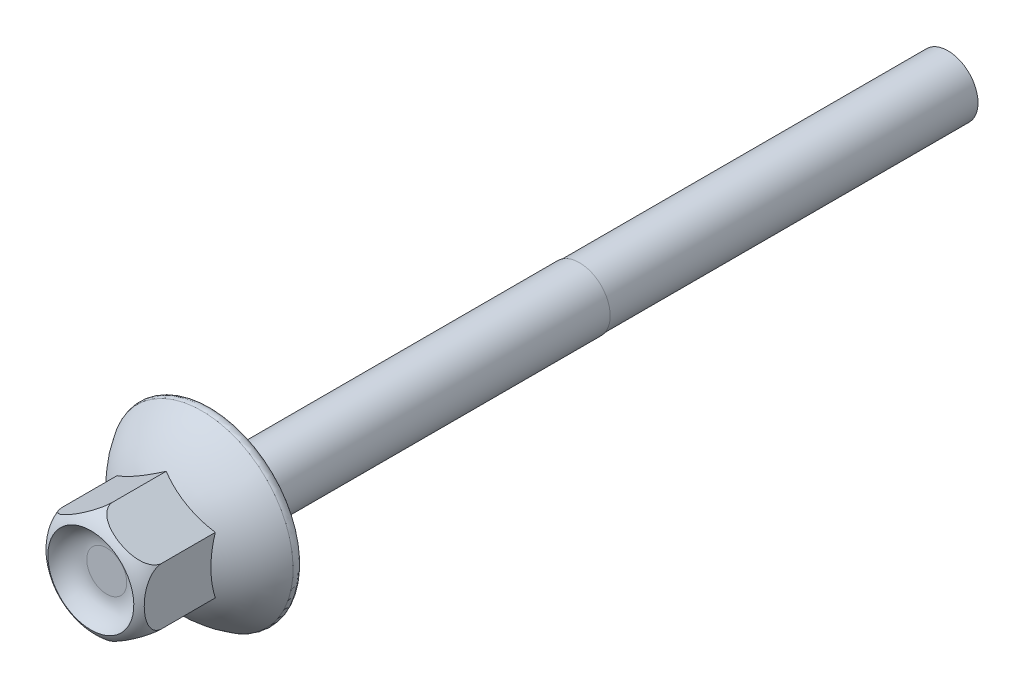
SolidWorks part; units mm, degrees
note: '?' marks a value the reader was unsure of.
ref_plane "Plane1" through (0, 0, 0) normal (0, 0, 1) x (1, 0, 0)
ref_plane "Plane2" through (0, 0, 0) normal (0, 1, 0) x (-1, 0, 0)
ref_plane "Plane3" through (0, 0, 0) normal (1, 0, 0) x (0, 0, -1)
sketch "Head Sketch" plane through (0, 0, 0) normal (0, 0, 1) x (1, 0, 0)
  line L0 (0, 4.6188) -> (4, 2.3094)
  line L1 (4, 2.3094) -> (4, -2.3094)
  line L2 (4, -2.3094) -> (0, -4.6188)
  line L3 (0, -4.6188) -> (-4, -2.3094)
  line L4 (-4, -2.3094) -> (-4, 2.3094)
  line L5 (-4, 2.3094) -> (0, 4.6188)
  line L6 (4, 2.3094) -> (-4, -2.3094) construction
  line L7 (0, 4.6188) -> (0, -4.6188) construction
  line L8 (-4, 2.3094) -> (4, -2.3094) construction
  point P0 (0, 0)
  dimension "D1" = 60
  dimension "D2" = 60
  dimension "Width across flats" = 8
extrude "Head" add sketch "Head Sketch" along normal blind 10
sketch "Shank Sketch" plane through (0, 0, 0) normal (0, 0, 1) x (1, 0, 0)
  line L0 (50, 0) -> (-50, 0) construction
  line L1 (0, -50) -> (0, 50) construction
  circle A0 centre (0, 0) radius 2.5
  dimension "Shank diameter" = 5
extrude "Shank" add sketch "Shank Sketch" against normal blind 60
sketch "Sketch3" plane through (0, 0, 0) normal (0, 1, 0) x (-1, 0, 0)
  line L0 (0, 0) -> (0, 10) construction
  line L1 (0, -60) -> (0, 0) construction
  line L4 (-7, 0) -> (0, 0)
  line L5 (0, 0) -> (0, 5)
  arc A0 (0, 5) -> (-7.4308, 0.7538) centre (0, -3.625) ccw
  arc A1 (-7, 0) -> (-7.4308, 0.7538) centre (-7, 0.5) cw
  dimension "D1" = 0.5
  dimension "D2" = 14
  dimension "D3" = 5
revolve "Flange" add sketch "Sketch3" angle 360 about L0
ref_axis "Axis1" through (0, 0, -110) along (0, 0, 1)?
sketch "Sketch5" plane through (0, 0, 0) normal (1, 0, 0) x (0, 0, -1)
  line L0 (-10, -2.6188) -> (-10, -4.6188)
  line L1 (-10, -4.6188) -> (-8, -4.6188)
  line L2 (-10, -4.6188) -> (-3.659, -4.6188) construction
  line L3 (-10, -4.6188) -> (-10, -2.3094) construction
  line L5 (-15.0856, 0) -> (-8.1394, 0) construction
  line L6 (50, 0) -> (-50, 0) construction
  arc A0 (-10, -2.6188) -> (-8, -4.6188) centre (-8, -2.6188) ccw
  dimension "D1" = 2
revolve "Head Trim" cut sketch "Sketch5" angle 360 about L5
sketch "Sketch6" plane through (0, 0, 10) normal (0, 0, 1) x (1, 0, 0)
  circle A3 centre (0, 0) radius 3.5
  dimension "D1" = 7
extrude "Head Cut" cut sketch "Sketch6" against normal blind 1.5
fillet "Fillet1" radius 2 1 edges at (3.5, 0, 8.5)
fillet "Fillet2" radius 0.5 1 edges at (-2.5, 0, 0)
sketch "Thread End" plane through (0, 0, 0) normal (1, 0, 0) x (0, 0, -1)
  line L0 (30, 2.5) -> (30, 2.45)
  line L1 (60, 2.5) -> (0.5, 2.5) construction
  line L2 (30, 2.45) -> (60, 2.45)
  line L3 (60, 2.5) -> (30, 2.5)
  line L4 (21.5519, 0) -> (27.4271, 0) construction
  line L5 (60, 0) -> (0.5, 0) construction
  line L6 (60, -2.5) -> (60, 2.5) construction
  line L7 (60, 2.45) -> (60, 2.5)
  dimension "D1" = 0.05
  dimension "Length of thread" = 30
revolve "Thread Cut" cut sketch "Thread End" angle 360 about L4
cosmetic thread "Cosmetic Thread2" parameters "D2"=11
equation "\"D1@Sketch6\" = \"Width across flats@Head Sketch\"*7/8"
